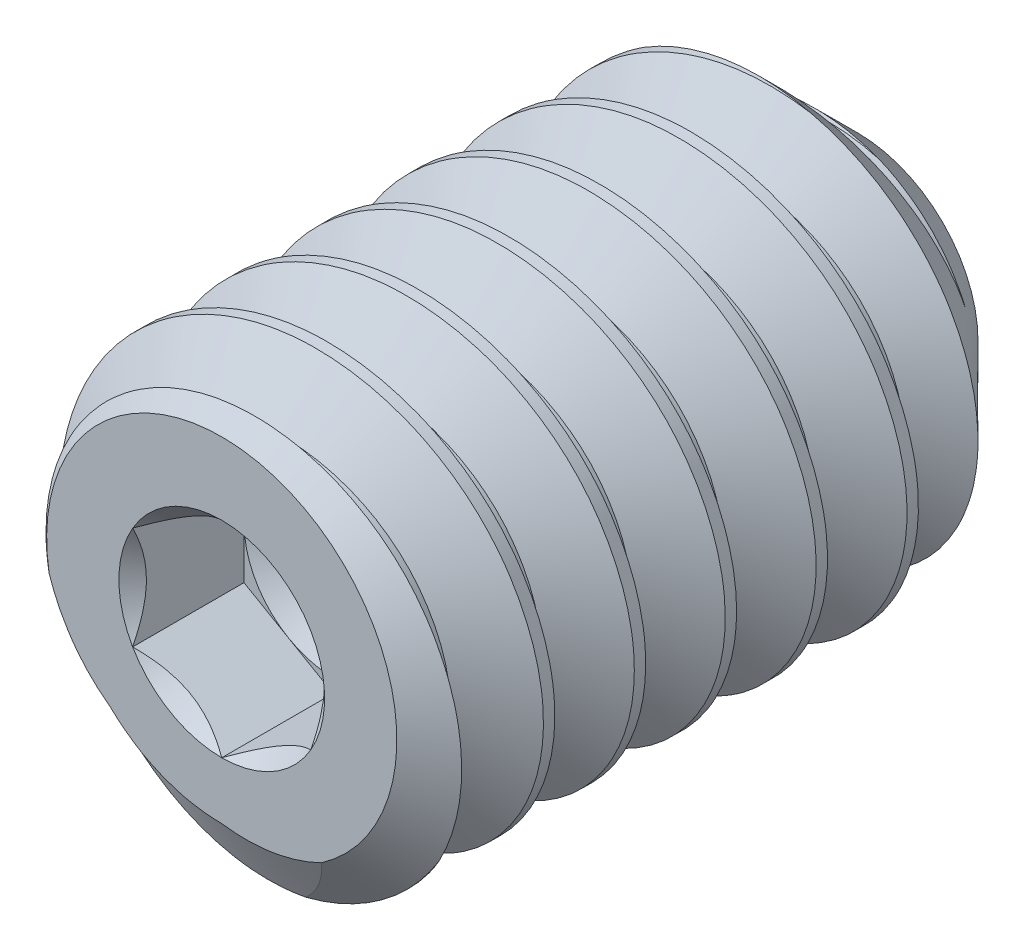
SolidWorks part; units mm, degrees
ref_plane "Front" through (0, 0, 0) normal (0, 0, 1) x (1, 0, 0)
ref_plane "Top" through (0, 0, 0) normal (0, 1, 0) x (1, 0, 0)
ref_plane "Right" through (0, 0, 0) normal (1, 0, 0) x (0, 0, -1)
sketch "Sketch22" plane through (0, 0, 0) normal (1, 0, 0) x (0, 0, -1)
  line L0 (-1.4077, 0) -> (-1.4077, 0.8738)
  line L1 (-1.4077, 0.8738) -> (-1.2547, 1.0922)
  line L2 (-1.2547, 1.0922) -> (1.2736, 1.0922)
  line L3 (1.2736, 1.0922) -> (1.7673, 0.5985)
  line L4 (1.7673, 0.5985) -> (1.4077, 0)
  line L5 (1.4077, 0) -> (-1.4077, 0)
  line L6 (1.4077, 0) -> (1.7673, 0) construction
  line L7 (1.7673, 0) -> (1.7673, 0.5985) construction
  line L8 (1.7673, -0.5985) -> (1.4077, 0) construction
  line L9 (-1.2547, -1.0922) -> (1.2736, -1.0922) construction
  dimension "Dia" = 2.1844
  dimension "Length" = 3.175
  dimension "D3" = 35
  dimension "D5" = 118
  dimension "D6" = 45
  dimension "D7" = 1.7475
revolve "Revolve1" add sketch "Sketch22" angle 360 about L6
ref_plane "Plane1" through (0, 0, -1.7673) normal (0, 0, 1) x (1, 0, 0)
sketch "Sketch27" plane through (0, 0, -1.7673) normal (0, 0, 1) x (1, 0, 0)
  circle A0 centre (0, 0) radius 1.0922 construction
  circle A1 centre (0, 0) radius 1.0922
curve "Helix/Spiral1" pitch 0.4536 height 3.6286 radius 1.0922 centre (0, 0, -1.7673) axis (0, 0, 1) start towards (0, 1, 0)
sketch "Sketch28" plane through (0, 0, 0) normal (1, 0, 0) x (0, 0, -1)
  line L0 (1.7673, 1.0922) -> (2.1642, 1.0922)
  line L1 (2.1642, 1.0922) -> (1.9941, 0.7976)
  line L2 (1.9941, 0.7976) -> (1.9374, 0.7976)
  line L3 (1.9374, 0.7976) -> (1.7673, 1.0922)
  line L4 (1.8523, 0.9449) -> (2.0791, 0.9449) construction
  line L6 (-1.2547, 1.0922) -> (1.2736, 1.0922) construction
  line L7 (1.7673, 1.2014) -> (1.7673, -1.2014) construction
  dimension "D1" = 0.0567
  dimension "D2" = 0.2268
  dimension "D3" = 60
sweep "Cut-Sweep2" cut profiles "Sketch28" path "Helix/Spiral1"
sketch "Sketch23" plane through (0, 0, 1.4077) normal (0, 0, 1) x (1, 0, 0)
  line L1 (0, 0.5133) -> (-0.4445, 0.2566)
  line L2 (-0.4445, 0.2566) -> (-0.4445, -0.2566)
  line L3 (-0.4445, -0.2566) -> (0, -0.5133)
  line L4 (0, -0.5133) -> (0.4445, -0.2566)
  line L5 (0.4445, -0.2566) -> (0.4445, 0.2566)
  line L6 (0.4445, 0.2566) -> (0, 0.5133)
  circle A0 centre (0, 0) radius 0.4445 construction
  dimension "Hex" = 0.889
extrude "Cut-Extrude10" cut sketch "Sketch23" against normal blind 0.5556
sketch "Sketch24" plane through (0, 0, 1.4077) normal (0, 0, 1) x (1, 0, 0)
  circle A0 centre (0, 0) radius 0.5133
extrude "Cut-Extrude11" cut sketch "Sketch24" against normal through all draft 45
sketch "Sketch26" plane through (0, 0, 0.8521) normal (0, 0, 1) x (1, 0, 0)
  circle A0 centre (0, 0) radius 0.4445 construction
  circle A1 centre (0, 0) radius 0.4445
extrude "Cut-Extrude12" cut sketch "Sketch26" against normal through all draft 60
sketch "Sketch30" plane through (0, 0, 0) normal (1, 0, 0) x (0, 0, -1)
  line L0 (-1.2547, 1.0922) -> (1.2736, 1.0922) construction
  line L1 (-1.4077, 0) -> (-1.4077, 0.8738) construction
  line L2 (1.7673, 0) -> (1.7673, 0.5985) construction
  line L3 (-1.2547, -1.0922) -> (1.2736, -1.0922) construction
  point P0 (-1.4077, 1.0922)
  point P1 (1.7673, 1.0922)
  point P2 (1.7673, -1.0922)
  point P11 (0.1798, -1.0922)
  dimension "D1" = 1.5875
sketch "Sketch31" plane through (0, 0, 0) normal (1, 0, 0) x (0, 0, -1)
  line L2 (1.4077, 0) -> (1.7673, -0.5985)
  line L3 (1.7673, 0.5985) -> (1.4077, 0)
equation "\"D7@Sketch22\"=\"Dia@Sketch22\"*.8"
equation "\"D1@Sketch28\" = \"D4@Helix/Spiral1\" * .125"
equation "\"D3@Helix/Spiral1\" = \"Length@Sketch22\" + \"D4@Helix/Spiral1\""
equation "\"D1@Sketch30\" = \"D4@Helix/Spiral1\" * 3.5"
equation "\"hex Depth@Cut-Extrude10\" = \"Hex@Sketch23\" * .625"
equation "\"D2@Sketch28\" = \"D4@Helix/Spiral1\" * .5"
